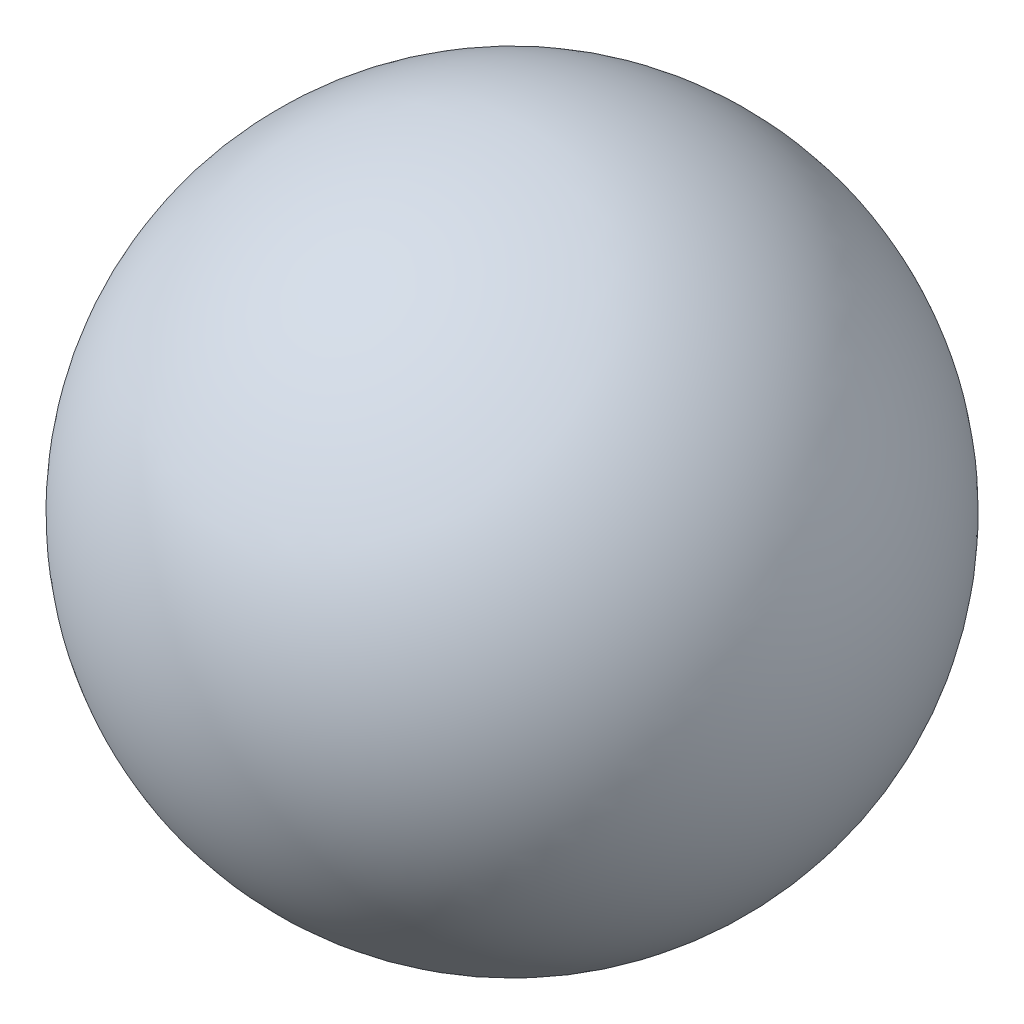
SolidWorks part; units mm, degrees
ref_plane "Front Plane" through (0, 0, 0) normal (0, 0, 1) x (1, 0, 0)
ref_plane "Top Plane" through (0, 0, 0) normal (0, 1, 0) x (1, 0, 0)
ref_plane "Right Plane" through (0, 0, 0) normal (1, 0, 0) x (0, 0, -1)
sketch "Sketch1" plane through (0, 0, 0) normal (0, 1, 0) x (1, 0, 0)
  line L0 (0, -1000) -> (0, 49000) construction
  circle A0 centre (0, 0) radius 88.9
  dimension "D1" = 177.8
revolve "Revolve3" add sketch "Sketch1" angle 360 about L0 region at (-37.7303, 0, 0)
